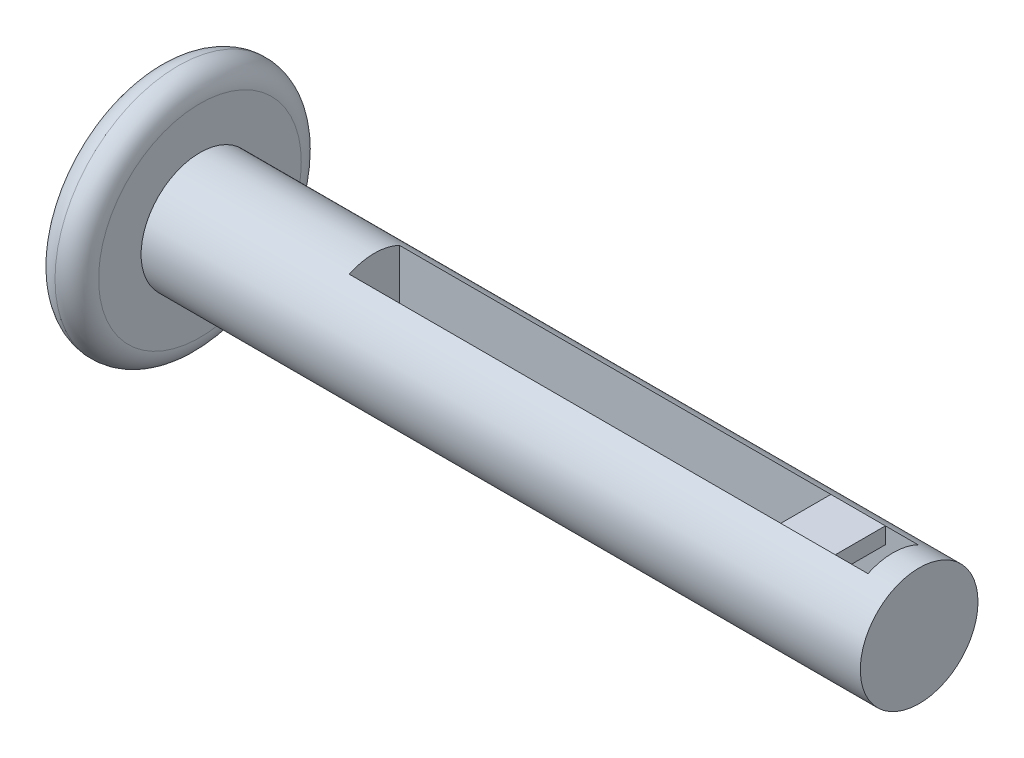
SolidWorks part; units mm, degrees
material "ABS"
ref_plane "Front Plane" through (0, 0, 0) normal (0, 0, 1) x (1, 0, 0)
ref_plane "Top Plane" through (0, 0, 0) normal (0, 1, 0) x (1, 0, 0)
ref_plane "Right Plane" through (0, 0, 0) normal (1, 0, 0) x (0, 0, -1)
sketch "Sketch1" plane through (0, 0, 0) normal (1, 0, 0) x (0, 0, -1)
  circle A0 centre (0, 0) radius 143.51
  dimension "D1" = 287.02
extrude "Boss-Extrude1" add sketch "Sketch1" along normal blind 50.8
sketch "Sketch2" plane through (50.8, 0, 0) normal (1, 0, 0) x (0, 0, -1)
  circle A0 centre (0, 0) radius 68.58
  dimension "D1" = 137.16
extrude "Boss-Extrude2" add sketch "Sketch2" along normal blind 838.2
sketch "Sketch3" plane through (0, 0, 0) normal (0, 1, 0) x (1, 0, 0)
  line L1 (254, -29.21) -> (858.52, -29.21)
  line L2 (254, -29.21) -> (254, 29.21)
  line L3 (254, 29.21) -> (858.52, 29.21)
  line L4 (858.52, -29.21) -> (858.52, 29.21)
  line L5 (254, -29.21) -> (858.52, 29.21) construction
  line L6 (254, 29.21) -> (858.52, -29.21) construction
  line L7 (0, 143.51) -> (0, -143.51) construction
  point P0 (556.26, 0)
  dimension "D1" = 58.42
  dimension "D2" = 604.52
  dimension "D3" = 254
extrude "Cut-Extrude1" cut sketch "Sketch3" against normal through all both and the other way through all
sketch "Sketch4" plane through (0, 0, 0) normal (-1, 0, 0) x (0, 0, 1)
  circle A0 centre (0, 0) radius 50.8
  dimension "D1" = 101.6
extrude "Cut-Extrude2" cut sketch "Sketch4" against normal blind 236.22
sketch "Sketch5" plane through (0, 0, 0) normal (0, 0, 1) x (1, 0, 0)
  line L0 (858.52, 62.0483) -> (254, 62.0483) construction
  line L1 (820.42, 62.0483) -> (756.92, 62.0483)
  line L2 (820.42, 62.0483) -> (820.42, 42.9983)
  line L3 (820.42, 42.9983) -> (756.92, 42.9983)
  line L4 (756.92, 62.0483) -> (756.92, 42.9983)
  line L5 (858.52, 68.58) -> (858.52, 62.0483) construction
  dimension "D1" = 38.1
  dimension "D2" = 63.5
  dimension "D3" = 19.05
extrude "Boss-Extrude3" add sketch "Sketch5" against normal mid plane 58.42
fillet "Fillet1" radius 25.4 2 edges at (0, 0, -143.51) (50.8, 0, -143.51)
scale "Scale1" bodies to scale 105 scale about centroid uniform scaling yes scale factor 0.05
